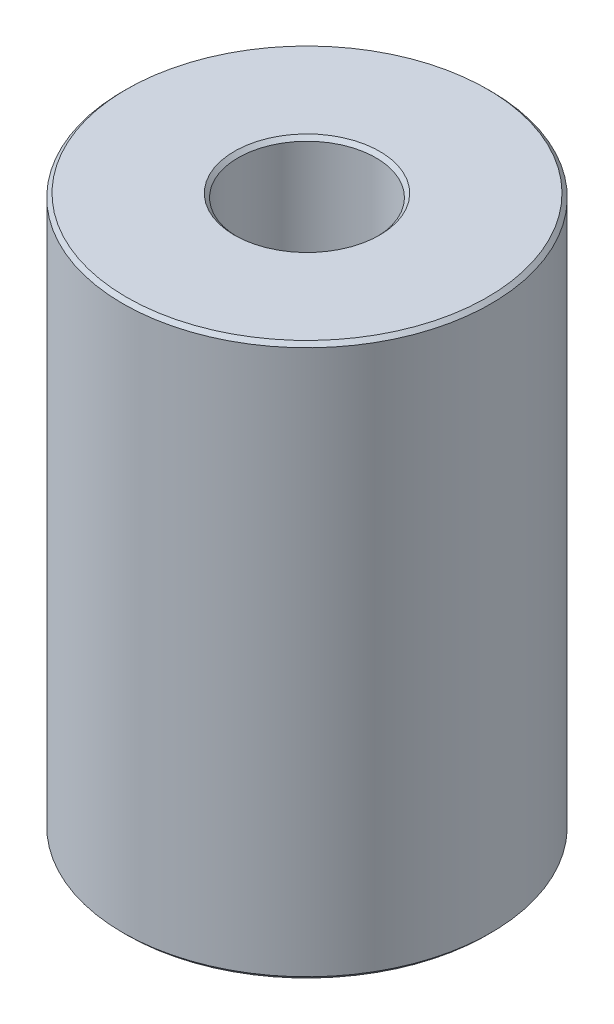
SolidWorks part; units mm, degrees
ref_plane "Front Plane" through (0, 0, 0) normal (0, 0, 1) x (1, 0, 0)
ref_plane "Top Plane" through (0, 0, 0) normal (0, 1, 0) x (1, 0, 0)
ref_plane "Right Plane" through (0, 0, 0) normal (1, 0, 0) x (0, 0, -1)
sketch "Sketch1" plane through (0, 0, 0) normal (0, 1, 0) x (1, 0, 0)
  circle A0 centre (0, 0) radius 12.5
  dimension "SLEEVE_OD" = 25
extrude "Boss-Extrude1" add sketch "Sketch1" along normal blind 37.5008
sketch "Sketch2" plane through (0, 0, 0) normal (0, 1, 0) x (1, 0, 0)
  circle A0 centre (0, 0) radius 4.6822
  dimension "BORE_D" = 9.3644
extrude "Cut-Extrude1" cut sketch "Sketch2" along normal through all
chamfer "Chamfer1" distance 0.2516 angle 45.182 4 edges at (0, 37.5008, 4.6822) (0, 0, 4.6822) (0, 0, 12.5) (0, 37.5008, 12.5) first distance on face at (0, 37.5008, 4.6822) first distance on face at (0, 0, 4.6822) first distance on face at (0, 37.5008, 12.5)
